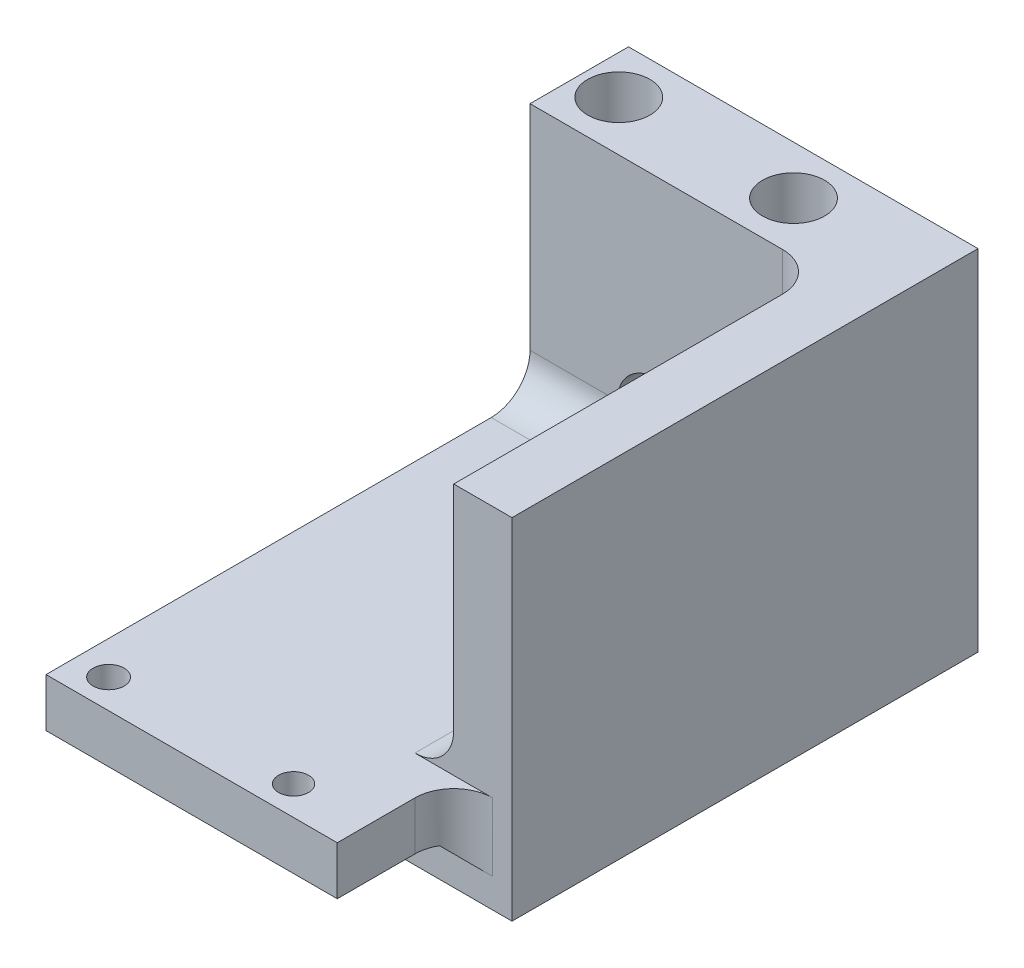
SolidWorks part; units mm, degrees
ref_plane "Front Plane" through (0, 0, 0) normal (0, 0, 1) x (1, 0, 0)
ref_plane "Top Plane" through (0, 0, 0) normal (0, 1, 0) x (1, 0, 0)
ref_plane "Right Plane" through (0, 0, 0) normal (1, 0, 0) x (0, 0, -1)
sketch "Sketch2" plane through (0, 0, 0) normal (0, 1, 0) x (1, 0, 0)
  line L1 (0, 0) -> (30, 0)
  line L2 (0, 0) -> (0, 60)
  line L3 (0, 60) -> (30, 60)
  line L4 (30, 0) -> (30, 60)
  circle A0 centre (3.45, 3) radius 1.6
  circle A1 centre (22.5, 3) radius 1.5445
  circle A2 centre (4, 55) radius 1.6
  circle A3 centre (22, 55) radius 1.6
  dimension "D3" = 3.2
  dimension "D8" = 3.2
  dimension "D9" = 3.2
  dimension "D1" = 30
  dimension "D2" = 3
  dimension "D4" = 19.05
  dimension "D5" = 7.5
  dimension "D6" = 60
  dimension "D7" = 4
  dimension "D10" = 5
  dimension "D11" = 5
  dimension "D12" = 8
extrude "Boss-Extrude1" add sketch "Sketch2" along normal blind 36
sketch "Sketch3" plane through (0, 36, 0) normal (0, 1, 0) x (1, 0, 0)
  line L0 (30, 0) -> (30, 60) construction
  line L1 (0, 0) -> (30, 0)
  line L2 (0, 0) -> (0, 49.856)
  line L3 (0, 49.856) -> (30, 49.856)
  line L4 (30, 0) -> (30, 49.856)
extrude "Cut-Extrude1" cut sketch "Sketch3" against normal blind 26
sketch "Sketch4" plane through (0, 0, 0) normal (0, -1, 0) x (1, 0, 0)
  line L0 (30, 0) -> (30, -60) construction
  line L1 (0, 0) -> (30, 0)
  line L2 (0, 0) -> (0, -12)
  line L3 (0, -12) -> (30, -12)
  line L4 (30, 0) -> (30, -12)
  dimension "D1" = 12
extrude "Cut-Extrude2" cut sketch "Sketch4" against normal blind 5
sketch "Sketch5" plane through (0, 36, 0) normal (0, 1, 0) x (1, 0, 0)
  circle A0 centre (4, 55) radius 3.2
  circle A1 centre (22, 55) radius 3.2
  dimension "D1" = 6.4
  dimension "D2" = 6.4
extrude "Cut-Extrude3" cut sketch "Sketch5" against normal blind 26
sketch "Sketch6" plane through (0, 0, -60) normal (0, 0, -1) x (-1, 0, 0)
  line L0 (-30, 0) -> (0, 0) construction
  circle A0 centre (-13, 14) radius 4
  dimension "D2" = 8
  dimension "D1" = 14
extrude "Cut-Extrude4" cut sketch "Sketch6" against normal blind 26
sketch "Sketch7" plane through (30, 0, 0) normal (1, 0, 0) x (0, 0, -1)
  line L0 (12, 0) -> (60, 0) construction
  line L1 (60, 36) -> (49.856, 36)
  line L2 (60, 36) -> (60, 0)
  line L3 (60, 0) -> (49.856, 0)
  line L4 (49.856, 36) -> (49.856, 0)
sketch "Sketch8" plane through (30, 0, 0) normal (1, 0, 0) x (0, 0, -1)
  line L1 (12, 0) -> (60, 0)
  line L2 (12, 0) -> (12, 36)
  line L3 (12, 36) -> (60, 36)
  line L4 (60, 0) -> (60, 36)
extrude "Boss-Extrude3" add sketch "Sketch8" along normal blind 6
chamfer "Chamfer1" distance 2 angle 45 1 edges at (15, 5, -12)
fillet "Fillet1" radius 4 1 edges at (30, 6.5, -12)
fillet "Fillet2" radius 4 4 edges at (6.5, 10, -49.856) (30, 23, -49.856) (30, 10, -30.928) (21.5, 10, -49.856)
